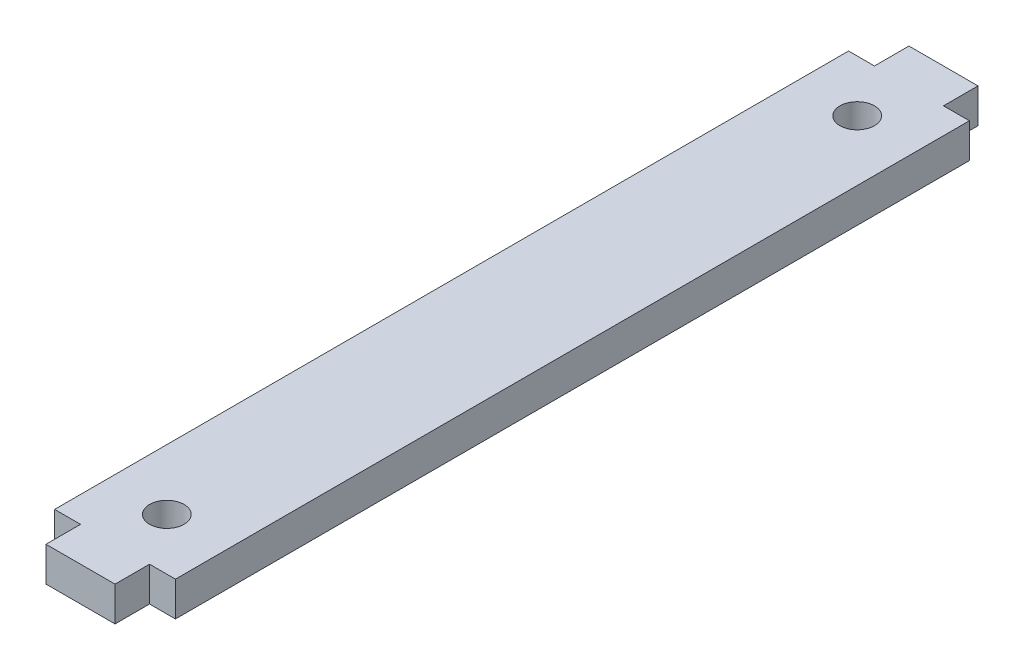
SolidWorks part; units mm, degrees
material "Beech"
ref_plane "Front Plane" through (0, 0, 0) normal (0, 0, 1) x (1, 0, 0)
ref_plane "Top Plane" through (0, 0, 0) normal (0, 1, 0) x (1, 0, 0)
ref_plane "Right Plane" through (0, 0, 0) normal (1, 0, 0) x (0, 0, -1)
sketch "Sketch1" plane through (0, 0, 0) normal (0, 1, 0) x (1, 0, 0)
  line L0 (-8.89, 0) -> (8.89, 0) construction
  line L1 (8.89, 58.42) -> (-8.89, 58.42)
  line L2 (8.89, 58.42) -> (8.89, -58.42)
  line L3 (8.89, -58.42) -> (-8.89, -58.42)
  line L4 (-8.89, 58.42) -> (-8.89, -58.42)
  line L5 (8.89, 58.42) -> (-8.89, -58.42) construction
  line L6 (8.89, -58.42) -> (-8.89, 58.42) construction
  line L7 (-5.08, 58.42) -> (5.08, 58.42)
  line L8 (-5.08, 58.42) -> (-5.08, 63.5)
  line L9 (-5.08, 63.5) -> (5.08, 63.5)
  line L10 (5.08, 58.42) -> (5.08, 63.5)
  line L11 (-5.08, 58.42) -> (5.08, 63.5) construction
  line L12 (-5.08, 63.5) -> (5.08, 58.42) construction
  line L13 (-5.08, -63.5) -> (5.08, -58.42) construction
  line L14 (-5.08, -58.42) -> (5.08, -63.5) construction
  line L15 (5.08, -58.42) -> (5.08, -63.5)
  line L16 (-5.08, -63.5) -> (5.08, -63.5)
  line L17 (-5.08, -58.42) -> (-5.08, -63.5)
  line L18 (-5.08, -58.42) -> (5.08, -58.42)
  line L19 (0, 58.42) -> (0, 50.8) construction
  circle A0 centre (0, 50.8) radius 2.54
  circle A1 centre (0, -50.8) radius 2.54
  point P0 (0, 0)
  point P10 (0, 60.96)
  point P17 (0, -60.96)
  point P21 (0.4991, 50.8164)
  dimension "D6" = 5.08
  dimension "D1" = 17.78
  dimension "D2" = 116.84
  dimension "D3" = 10.16
  dimension "D4" = 3.81
  dimension "D5" = 5.08
  dimension "D7" = 7.62
extrude "Boss-Extrude1" add sketch "Sketch1" along normal blind 5.08 contours L1 L4 L3 L2 | L3 L17 L16 L15 | L1 L10 L9 L8 region at (0, 0, 0) region at (0, 0, -60.96) region at (0, 0, 60.96)
